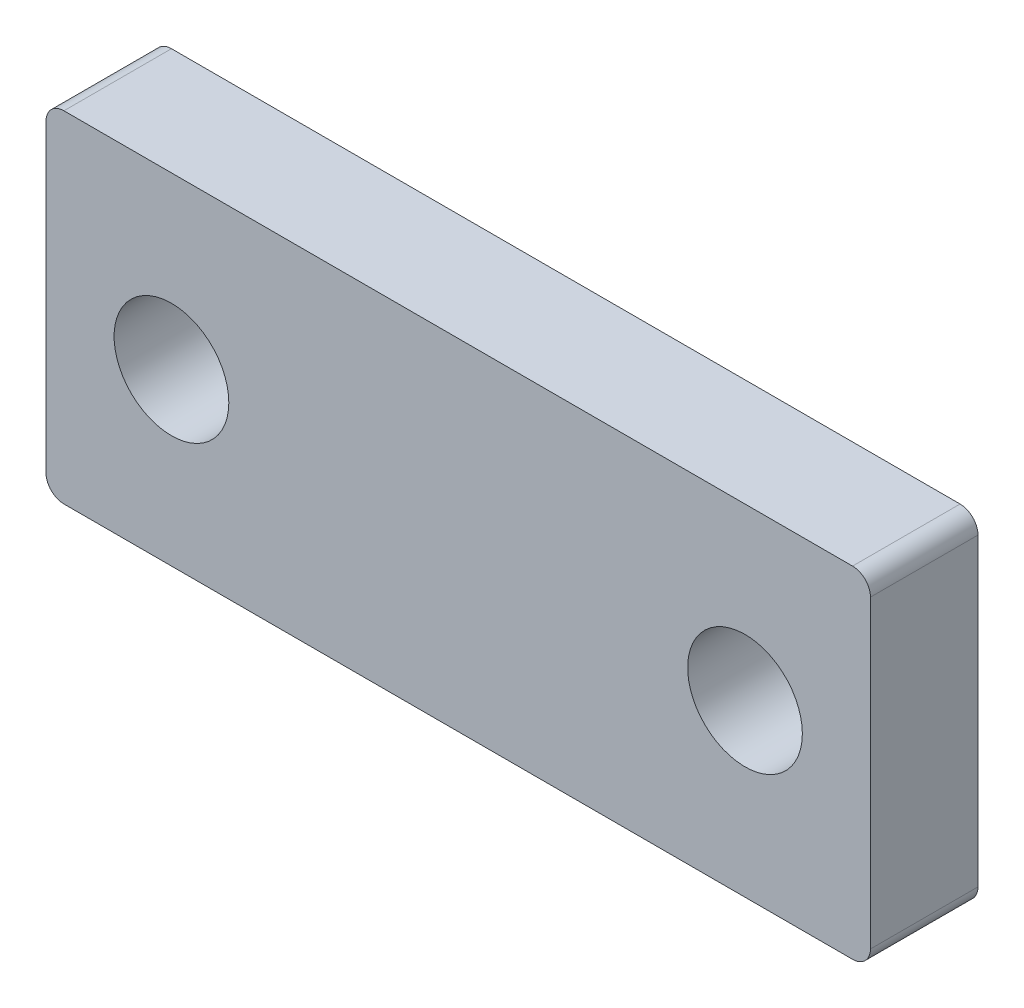
SolidWorks part; units mm, degrees
material "AISI 1045 Steel, cold drawn"
ref_plane "Front Plane" through (0, 0, 0) normal (0, 0, 1) x (1, 0, 0)
ref_plane "Top Plane" through (0, 0, 0) normal (0, 1, 0) x (1, 0, 0)
ref_plane "Right Plane" through (0, 0, 0) normal (1, 0, 0) x (0, 0, -1)
sketch "Sketch1" plane through (0, 0, 0) normal (0, 0, 1) x (1, 0, 0)
  line L0 (8, 0) -> (-8, 0) construction
  line L1 (11.5, -4.75) -> (-11.5, -4.75)
  line L2 (11.5, -4.75) -> (11.5, 4.75)
  line L3 (11.5, 4.75) -> (-11.5, 4.75)
  line L4 (-11.5, -4.75) -> (-11.5, 4.75)
  line L5 (11.5, -4.75) -> (-11.5, 4.75) construction
  line L6 (11.5, 4.75) -> (-11.5, -4.75) construction
  point P0 (0, 0)
  point P9 (0, 0)
  dimension "D1" = 9.5
  dimension "D2" = 23
  dimension "D3" = 16
extrude "Boss-Extrude1" add sketch "Sketch1" along normal blind 3
hole_wizard "M3 Clearance Hole1" positions "Sketch2" profile "Sketch3" hole size "M3" standard "ANSI Metric" end condition through all
sketch "Sketch2" plane through (0, 0, 3) normal (0, 0, 1) x (1, 0, 0)
  point P0 (-8, 0)
  point P3 (8, 0)
sketch "Sketch3" plane through (-8, 0, 3) normal (1, 0, 0) x (0, -1, 0)
  line L0 (0, 0) -> (0, 3)
  line L1 (0, 3) -> (1.6, 3)
  line L2 (1.6, 3) -> (1.6, 0)
  line L5 (1.6, 0) -> (0, 0)
  line L11 (0, -6.35) -> (0, 107.95) construction
  dimension "Thru Hole Dia." = 3.2
  dimension "Thru Hole Depth" = 3
fillet "Fillet1" radius 0.5 4 edges at (11.5, 4.75, 1.5) (11.5, -4.75, 1.5) (-11.5, -4.75, 1.5) (-11.5, 4.75, 1.5)
